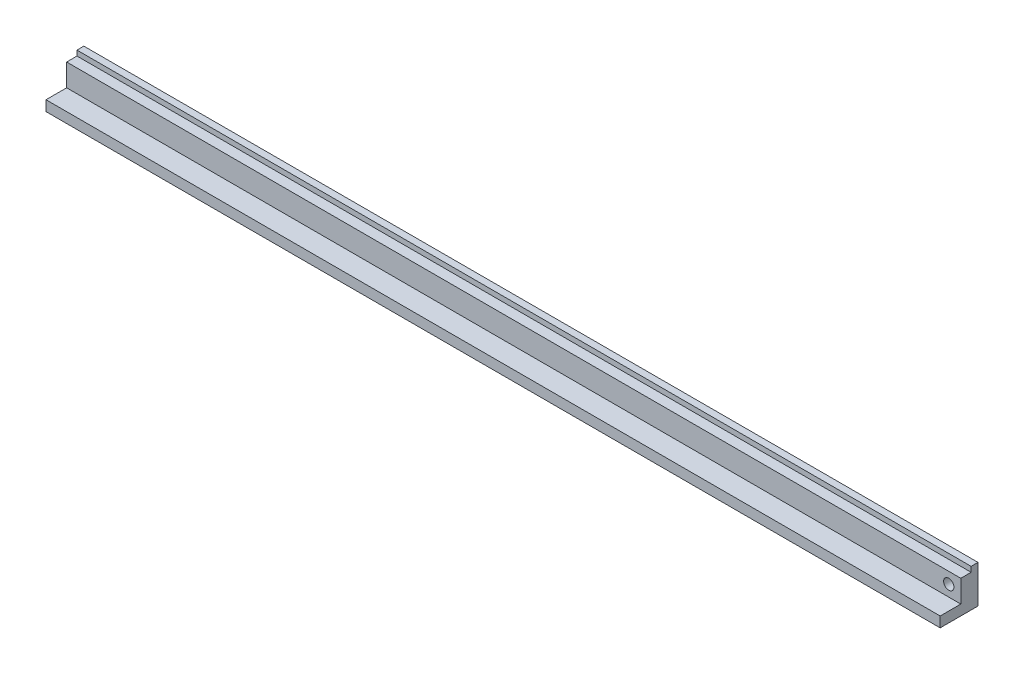
SolidWorks part; units mm, degrees
ref_plane "Спереди" through (0, 0, 0) normal (0, 0, 1) x (1, 0, 0)
ref_plane "Сверху" through (0, 0, 0) normal (0, 1, 0) x (1, 0, 0)
ref_plane "Справа" through (0, 0, 0) normal (1, 0, 0) x (0, 0, -1)
sketch "Эскиз1" plane through (0, 0, 0) normal (1, 0, 0) x (0, 0, -1)
  line L0 (0, 0) -> (-11, 0)
  line L1 (-11, 0) -> (-11, 3)
  line L2 (-11, 3) -> (-5, 3)
  line L3 (-5, 3) -> (-5, 9.5)
  line L4 (-5, 9.5) -> (-2, 9.5)
  line L5 (-2, 9.5) -> (-2, 11)
  line L6 (-2, 11) -> (0, 11)
  line L7 (0, 11) -> (0, 0)
  dimension "D1" = 5
  dimension "D2" = 11
  dimension "D3" = 3
  dimension "D4" = 6
  dimension "D5" = 6.5
  dimension "D6" = 11
  dimension "D7" = 1.5
  dimension "D8" = 2
extrude "Бобышка-Вытянуть1" add sketch "Эскиз1" along normal blind 260
sketch "Эскиз2" plane through (0, 0, 5) normal (0, 0, 1) x (1, 0, 0)
  line L1 (260, 9.5) -> (0, 9.5) construction
  line L2 (260, 9.5) -> (260, 3) construction
  circle A0 centre (256.5, 6.25) radius 1.5
  dimension "D1" = 3
  dimension "D2" = 3.5
  dimension "D3" = 3.25
extrude "Вырез-Вытянуть1" cut sketch "Эскиз2" against normal through all
